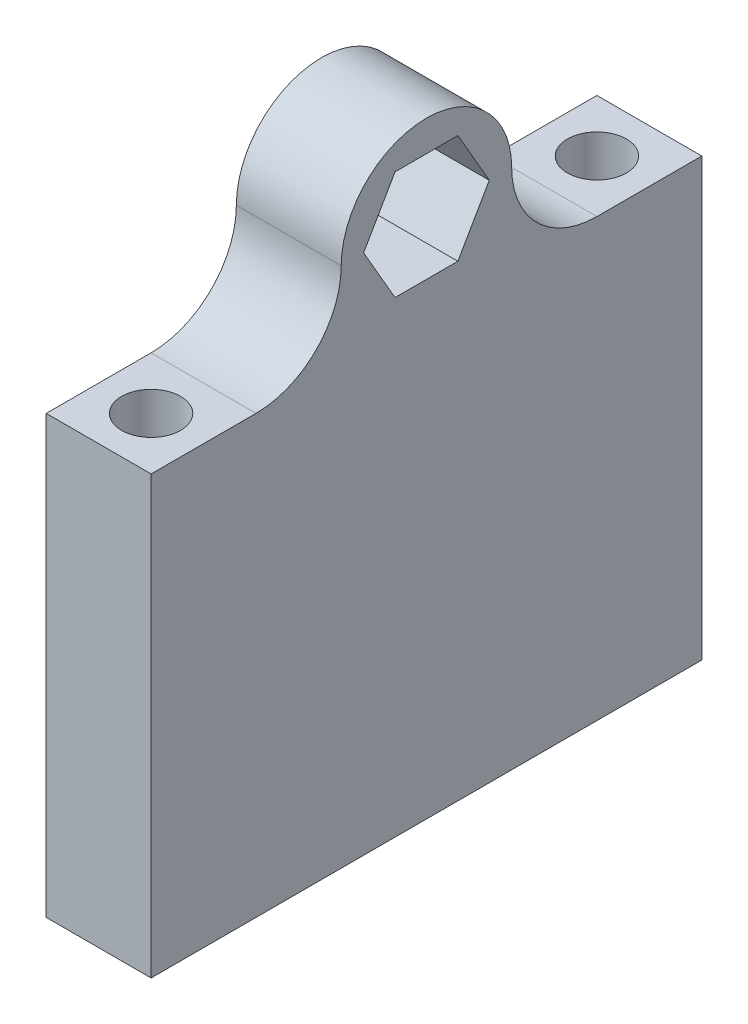
SolidWorks part; units mm, degrees
ref_plane "Спереди" through (0, 0, 0) normal (0, 0, 1) x (1, 0, 0)
ref_plane "Сверху" through (0, 0, 0) normal (0, 1, 0) x (1, 0, 0)
ref_plane "Справа" through (0, 0, 0) normal (1, 0, 0) x (0, 0, -1)
sketch "Эскиз1" plane through (0, 0, 0) normal (1, 0, 0) x (0, 0, -1)
  line L0 (-13, -6.5) -> (-21, -6.5)
  line L1 (-21, -39.795) -> (21, -39.795)
  line L2 (-21, -39.795) -> (-21, -6.5)
  line L4 (21, -39.795) -> (21, -6.5)
  line L5 (13, -6.5) -> (21, -6.5)
  arc A0 (6.5, 0) -> (-6.5, 0) centre (0, 0) ccw
  arc A1 (-13, -6.5) -> (-6.5, 0) centre (-13, 0) ccw
  arc A2 (6.5, 0) -> (13, -6.5) centre (13, 0) ccw
  point P4 (18, -11.5)
  point P5 (0, 0)
  point P7 (0, -39.795)
  point P9 (0, 6.5)
  dimension "D1" = 13
  dimension "D4" = 13
  dimension "D5" = 13
  dimension "D6" = 14.5
  dimension "D2" = 33.295
  dimension "D3" = 39.795
extrude "Бобышка-Вытянуть1" add sketch "Эскиз1" along normal blind 8
sketch "Эскиз2" plane through (8, 0, 0) normal (1, 0, 0) x (0, 0, -1)
  line L1 (4.792, 0) -> (2.396, 4.15)
  line L2 (2.396, 4.15) -> (-2.396, 4.15)
  line L3 (-2.396, 4.15) -> (-4.792, 0)
  line L4 (-4.792, 0) -> (-2.396, -4.15)
  line L5 (-2.396, -4.15) -> (2.396, -4.15)
  line L6 (2.396, -4.15) -> (4.792, 0)
  circle A0 centre (0, 0) radius 4.15 construction
  dimension "D1" = 8.3
extrude "Вырез-Вытянуть1" cut sketch "Эскиз2" against normal through all
sketch "Эскиз3" plane through (0, -6.5, 0) normal (0, 1, 0) x (1, 0, 0)
  line L0 (4, -17.0018) -> (4, 17.0018) construction
  line L3 (0, 0) -> (8, 0) construction
  line L6 (8, -6.5) -> (8, 6.5) construction
  circle A0 centre (4, 17.0018) radius 2.25
  circle A1 centre (4, -17.0018) radius 2.25
  point P5 (4, 0)
  point P9 (4, 0)
  dimension "D1" = 4.5
  dimension "D2" = 34.0036
  dimension "D3" = 4.5
extrude "Вырез-Вытянуть2" cut sketch "Эскиз3" against normal through all
